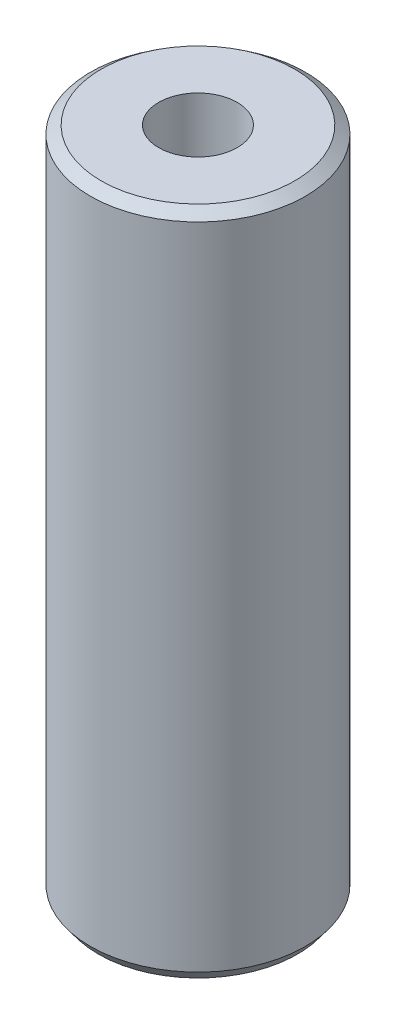
SolidWorks part; units mm, degrees
ref_plane "Front Plane" through (0, 0, 0) normal (0, 0, 1) x (1, 0, 0)
ref_plane "Top Plane" through (0, 0, 0) normal (0, 1, 0) x (1, 0, 0)
ref_plane "Right Plane" through (0, 0, 0) normal (1, 0, 0) x (0, 0, -1)
sketch "Sketch1" plane through (0, 0, 0) normal (0, 1, 0) x (1, 0, 0)
  circle A0 centre (0, 0) radius 52.5
  dimension "SHAFT_OD" = 105
extrude "Boss-Extrude1" add sketch "Sketch1" along normal blind 326.3587
sketch "Sketch2" plane through (0, 0, 0) normal (0, 1, 0) x (1, 0, 0)
  circle A0 centre (0, 0) radius 19.1741
  dimension "BORE_D" = 38.3483
extrude "Cut-Extrude1" cut sketch "Sketch2" along normal through all
chamfer "Chamfer1" distance 3.8915 angle 53.361 2 edges at (0, 326.3587, 52.5) (0, 0, 52.5) first distance on face at (0, 326.3587, 52.5) first distance on face at (0, 0, 19.1741)
